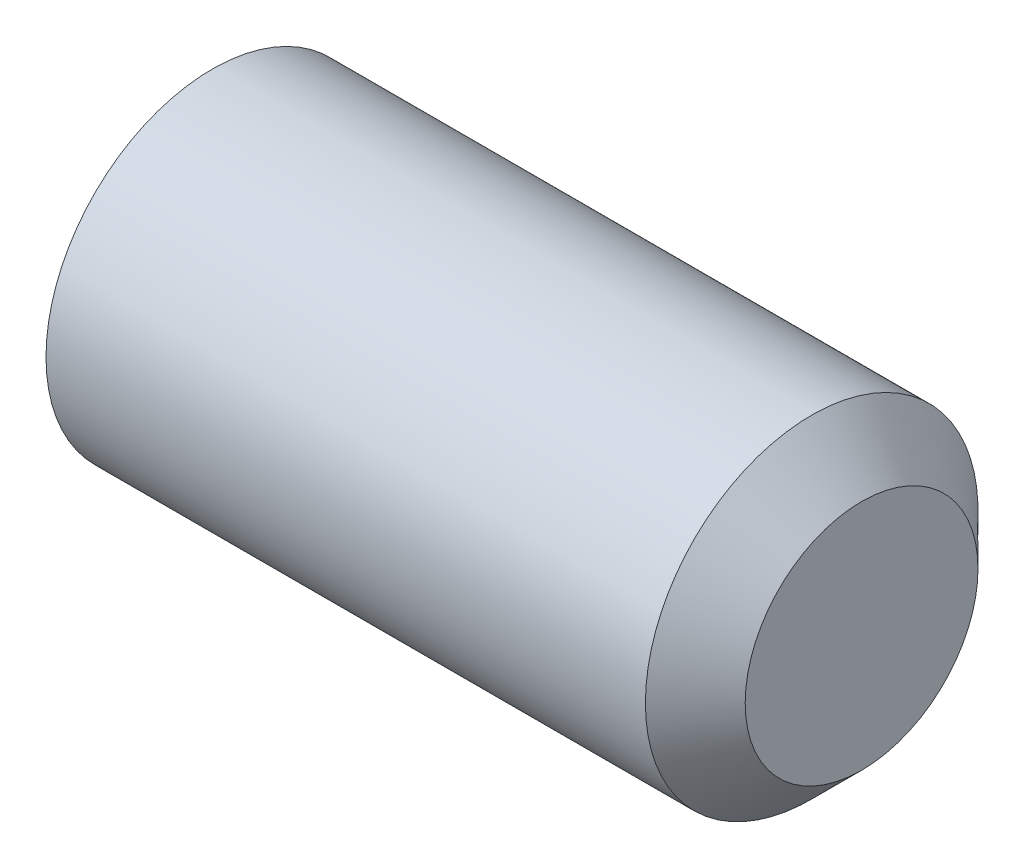
SolidWorks part; units mm, degrees
revolve "BaseBody" add sketch "BodySke" angle 360 about L5 other way angle 60
sketch "BodySke" plane through (0, 0, 0) normal (0, 0, 1) x (1, 0, 0)
  line L0 (0, 0) -> (0, 4.172)
  line L1 (0, 4.172) -> (0.478, 5)
  line L2 (0.478, 5) -> (18.5, 5)
  line L3 (18.5, 5) -> (20, 3.5)
  line L4 (20, 0) -> (0, 0)
  line L5 (-12.7, 0) -> (88.9, 0) construction
  line L6 (20, 3.5) -> (20, 0)
  line L7 (20, 3.5) -> (20, 13.025) construction
  line L8 (0, -4.172) -> (0.478, -5) construction
  line L9 (1.5, 15.875) -> (1.5, -3.175) construction
  line L10 (18.5, -5) -> (20, -3.5) construction
  dimension "Length" = 20
  dimension "Diameter" = 10
cosmetic thread "ThreadCosmetic" parameters "Thread_minor"=8.344
ref_plane "Plane1" through (0, 0, 0) normal (0, 0, 1) x (1, 0, 0)
ref_plane "Plane2" through (0, 0, 0) normal (0, 1, 0) x (1, 0, 0)
ref_plane "Plane3" through (0, 0, 0) normal (1, 0, 0) x (0, 0, -1)
other "Configuration Table"
sketch "Sketch2" plane through (0, 0, 0) normal (-1, 0, 0) x (0, 0, 1)
  line L0 (1.4434, 2.5) -> (-1.4434, 2.5)
  line L1 (-1.4434, 2.5) -> (-2.8868, 0)
  line L2 (1.4434, 2.5) -> (2.8868, 0)
  line L3 (1.4434, -2.5) -> (2.8868, 0)
  line L4 (1.4434, -2.5) -> (-1.4434, -2.5)
  line L5 (-1.4434, -2.5) -> (-2.8868, 0)
  dimension "D2" = 2.5
  dimension "D3" = 2.5
extrude "Hex" cut sketch "Sketch2" against normal blind 5
sketch "Sketch4" plane through (0, 4.7709, -0.5249) normal (-1, 0, 0) x (0, 0, 1)
  line L0 (0.5249, -4.7709) -> (3.3314, -4.7709)
  line L1 (0.5249, -4.7709) -> (6.6732, -1.2211) construction
  line L2 (0.5249, -4.7709) -> (1.9281, -2.3404)
  line L3 (2.8584, -4.1568) -> (3.2099, -3.9539)
  line L4 (2.2234, -3.057) -> (2.5749, -2.8541)
  arc A0 (2.8584, -4.1568) -> (2.2234, -3.057) centre (0.5249, -4.7709) ccw
  arc A1 (3.3314, -4.7709) -> (3.2099, -3.9539) centre (0.5249, -4.7709) ccw
  arc A2 (1.9281, -2.3404) -> (2.5749, -2.8541) centre (0.5249, -4.7709) cw
  circle A3 centre (0.5249, -4.7709) radius 2.413 construction
  circle A4 centre (0.5249, -4.7709) radius 2.8065 construction
  dimension "Spline_n_dim" = 4.826
  dimension "Spline_m_dim" = 5.613
  dimension "D1" = 30
  dimension "Spline_p_dim" = 1.27
  dimension "D3" = 0.635
extrude "Spline6" [suppressed] cut sketch "Sketch4" against normal blind 5
pattern_circular "CirPattern1" [suppressed] count 6 every 60 about axis through (-12.7, 0, 0) along (1, 0, 0)
sketch "Sketch5" plane through (0, 0.6556, 6.6316) normal (-1, 0, 0) x (0, 0, 1)
  line L0 (-6.6316, -0.6556) -> (-3.8251, -0.6556)
  line L1 (-6.6316, -0.6556) -> (-1.6115, 4.3645) construction
  line L2 (-6.6316, -0.6556) -> (-6.6316, 2.1509)
  line L3 (-4.4764, 0.6017) -> (-4.2496, 0.8284)
  line L4 (-5.3744, 1.4997) -> (-5.1476, 1.7265)
  line L5 (-5.3744, 1.4997) -> (-4.4764, 0.6017)
  arc A1 (-3.8251, -0.6556) -> (-4.2496, 0.8284) centre (-6.6316, -0.6556) ccw
  arc A2 (-6.6316, 2.1509) -> (-5.1476, 1.7265) centre (-6.6316, -0.6556) cw
  circle A3 centre (-6.6316, -0.6556) radius 2.413 construction
  circle A4 centre (-6.6316, -0.6556) radius 2.8065 construction
  dimension "Spline_n_dim" = 4.826
  dimension "Spline_m_dim" = 5.613
  dimension "Spline_p_dim" = 1.27
  dimension "D3" = 0.635
  dimension "D1" = 45
  dimension "Spline_a_dim" = 90
extrude "Spline4" [suppressed] cut sketch "Sketch5" against normal blind 5
pattern_circular "CirPattern2" [suppressed] count 4 every 90 about axis through (-12.7, 0, 0) along (1, 0, 0)
sketch "ThdSchSke" plane through (0, 0, 0) normal (0, 0, 1) x (1, 0, 0)
  line L0 (0.478, -4.172) -> (-0.1017, -5)
  line L1 (0.478, -4.172) -> (1.0578, -5)
  line L2 (1.0578, -5) -> (1.0578, -6.25)
  line L3 (-3.175, 0) -> (5.1513, 0) construction
  line L4 (0.478, 5) -> (0.478, -5) construction
  line L5 (1.0578, -6.25) -> (-0.1017, -6.25)
  line L6 (-0.1017, -6.25) -> (-0.1017, -5)
  dimension "Thread_minor" = 8.344
  dimension "Diameter" = 10
revolve "ThreadSchematic" [suppressed] cut sketch "ThdSchSke" angle 360 about L3
pattern_linear "ThdSchPat" [suppressed]
equation "\"D2@Sketch2\" = \"Hex_size@Sketch2\" / 2"
equation "\"D3@Sketch2\" = \"Hex_size@Sketch2\" / 2"
equation "\"Thread_minor@ThreadCosmetic\" = \"Minor_dia@BodySke\""
equation "\"D1@Sketch4\" = \"Spline_a_dim@Sketch4\" / 2"
equation "\"D3@Sketch4\" = \"Spline_p_dim@Sketch4\" / 2"
equation "\"D2@CirPattern1\" = \"Spline_a_dim@Sketch4\""
equation "\"Num_teeth@CirPattern1\" = 360 / \"D2@CirPattern1\""
equation "\"Spline_a_dim@Sketch5\" = 90"
equation "\"Spline_p_dim@Sketch5\" = \"Spline_p_dim@Sketch4\""
equation "\"Spline_m_dim@Sketch5\" = \"Spline_m_dim@Sketch4\""
equation "\"Spline_n_dim@Sketch5\" = \"Spline_n_dim@Sketch4\""
equation "\"D1@Sketch5\" = \"Spline_a_dim@Sketch5\" / 2"
equation "\"D3@Sketch5\" = \"Spline_p_dim@Sketch5\" / 2"
equation "\"Key_eng@Spline4\" = \"Key_eng@Spline6\""
equation "\"Thread_minor@ThdSchSke\" = \"Thread_minor@ThreadCosmetic\""
equation "\"Diameter@ThdSchSke\" = \"Diameter@BodySke\""
equation "\"Overcut@ThdSchSke\" = \"Diameter@BodySke\" * 1.25"
equation "\"Num_threads@ThdSchPat\" = int( (\"Length@BodySke\" - ( ( ( \"Diameter@BodySke\" - \"Minor_dia@BodySke\" ) * 0.5 ) / tan( \"Drive_ch_ang@BodySke\" * 0.017453292 ) ) - ( ( ( \"Diameter@BodySke\" - \"Cup_dia@BodySke\" ) * 0.5 ) * tan( \"Cup_nose_ang@BodySke\" * 0.017453292 ) ) ) / \"Advance@BodySke\" + 0.999 )  + 1"
equation "\"Advance@ThdSchPat\" = (\"Length@BodySke\" - ( ( ( \"Diameter@BodySke\" - \"Minor_dia@BodySke\" ) * 0.5 ) / tan( \"Drive_ch_ang@BodySke\" * 0.017453292 ) ) - ( ( ( \"Diameter@BodySke\" - \"Cup_dia@BodySke\" ) * 0.5 ) * tan( \"Cup_nose_ang@BodySke\" * 0.017453292 ) ) ) /  (\"Num_threads@ThdSchPat\" - 1) 'relax it"
equation "' \"Num_threads@ThdSchPat\" = \"Num_threads@ThdSchPat\" - sgn( \"Num_threads@ThdSchPat\" - 1) '---chamfered tips only---"
